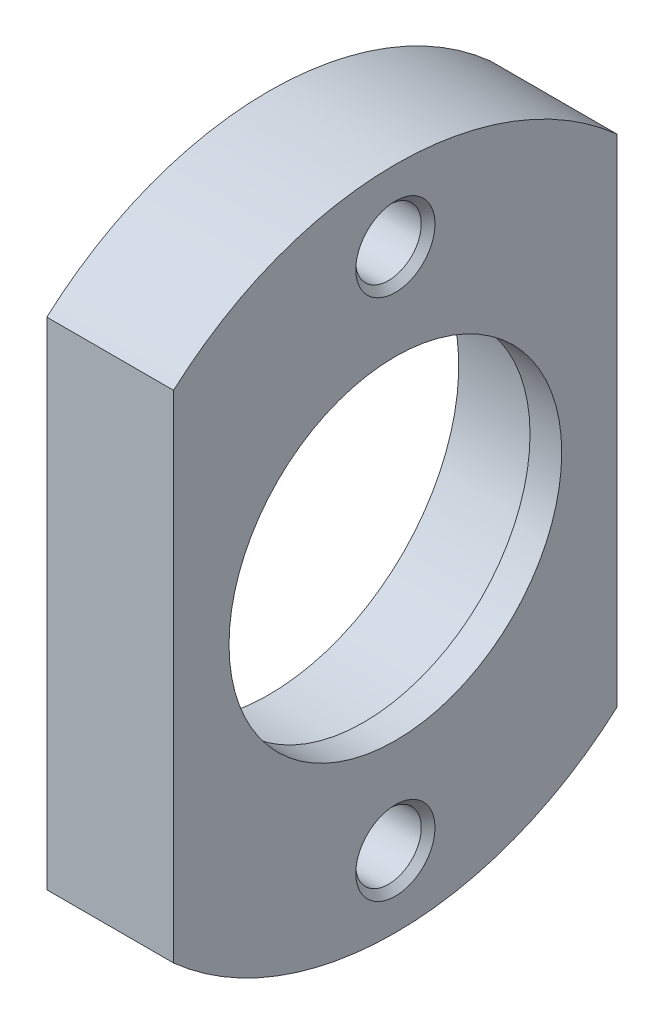
SolidWorks part; units mm, degrees
ref_plane "Front Plane" through (0, 0, 0) normal (0, 0, 1) x (1, 0, 0)
ref_plane "Top Plane" through (0, 0, 0) normal (0, 1, 0) x (1, 0, 0)
ref_plane "Right Plane" through (0, 0, 0) normal (1, 0, 0) x (0, 0, -1)
ref_plane "Plane1" through (0, 0, 0) normal (1, 0, 0) x (0, 0, -1)
sketch "Sketch1" plane through (0, 0, 0) normal (1, 0, 0) x (0, 0, -1)
  line L0 (14, -15.6525) -> (14, 15.6525)
  line L1 (-14, 15.6525) -> (-14, -15.6525)
  arc A0 (-14, -15.6525) -> (14, -15.6525) centre (0, 0) ccw
  arc A1 (14, 15.6525) -> (-14, 15.6525) centre (0, 0) ccw
extrude "Boss-Extrude1" add sketch "Sketch1" against normal blind 4 and the other way blind 4
ref_plane "Plane2" through (0, 0, 0) normal (0, 0, 1) x (1, 0, 0)
sketch "Sketch2" plane through (0, 0, 0) normal (0, 0, 1) x (1, 0, 0)
  line L0 (-4, 0) -> (-4, 12)
  line L1 (-4, 12) -> (2, 12)
  line L2 (2, 12) -> (2, 10.5)
  line L3 (2, 10.5) -> (4, 10.5)
  line L4 (4, 10.5) -> (4, 0)
  line L5 (4, 0) -> (-4, 0)
  line L6 (4, 0) -> (-4, 0) construction
revolve "Cut-Revolve1" cut sketch "Sketch2" angle 360 about L6 reverse direction yes
ref_plane "Plane3" through (0, 0, 0) normal (0, 0, 1) x (1, 0, 0)
sketch "Sketch3" plane through (0, 0, 0) normal (0, 0, 1) x (1, 0, 0)
  line L0 (-4, -16.5) -> (-4, -14)
  line L1 (-4, -14) -> (-3.567, -14.433)
  line L2 (-3.567, -14.433) -> (3.567, -14.433)
  line L3 (3.567, -14.433) -> (4, -14)
  line L4 (4, -14) -> (4, -16.5)
  line L5 (4, -16.5) -> (-4, -16.5)
  line L6 (4, -16.5) -> (-4, -16.5) construction
revolve "Cut-Revolve2" cut sketch "Sketch3" angle 360 about L6 reverse direction yes
ref_plane "Plane4" through (0, 0, 0) normal (0, 0, 1) x (1, 0, 0)
sketch "Sketch4" plane through (0, 0, 0) normal (0, 0, 1) x (1, 0, 0)
  line L0 (-4, 16.5) -> (-4, 19)
  line L1 (-4, 19) -> (-3.567, 18.567)
  line L2 (-3.567, 18.567) -> (3.567, 18.567)
  line L3 (3.567, 18.567) -> (4, 19)
  line L4 (4, 19) -> (4, 16.5)
  line L5 (4, 16.5) -> (-4, 16.5)
  line L6 (4, 16.5) -> (-4, 16.5) construction
revolve "Cut-Revolve3" cut sketch "Sketch4" angle 360 about L6 reverse direction yes
